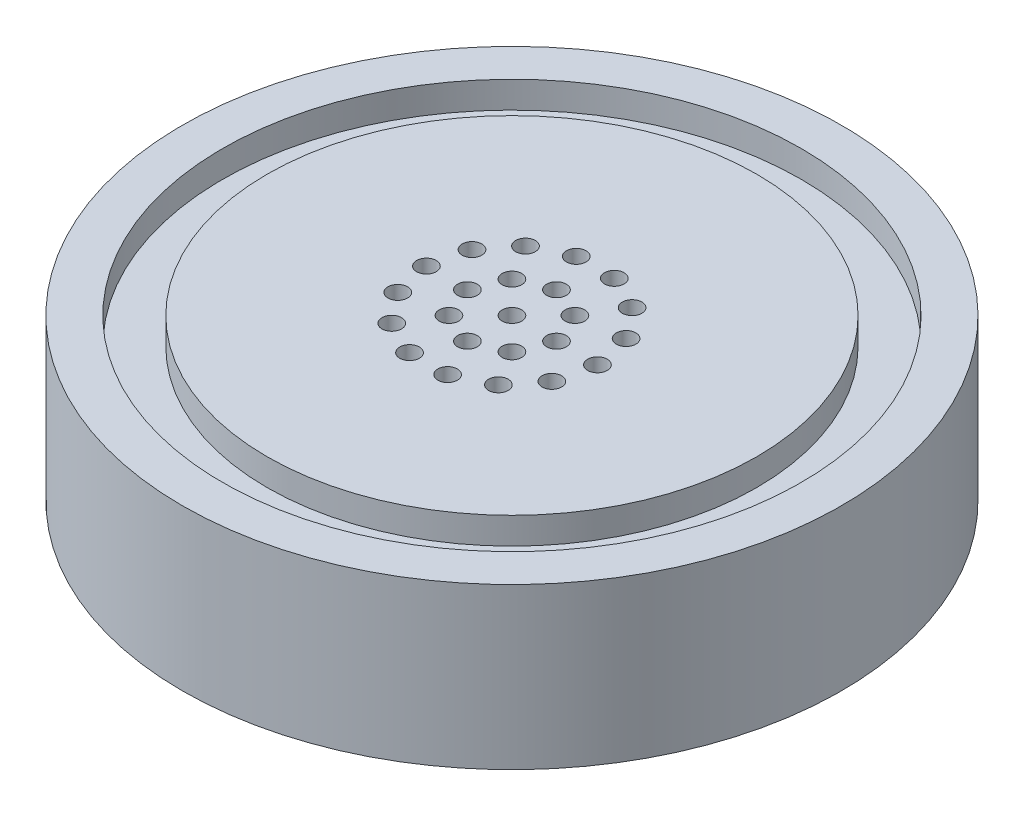
SolidWorks part; units mm, degrees
material "6061-T6 (SS)"
ref_plane "Front Plane" through (0, 0, 0) normal (0, 0, 1) x (1, 0, 0)
ref_plane "Top Plane" through (0, 0, 0) normal (0, 1, 0) x (1, 0, 0)
ref_plane "Right Plane" through (0, 0, 0) normal (1, 0, 0) x (0, 0, -1)
ref_axis "Axis1" through (0, -0.4763, 0) along (0, 1, 0)
sketch "Sketch2" plane through (0, 0, 0) normal (0, 1, 0) x (1, 0, 0)
  circle A0 centre (0, 0) radius 23.495
  dimension "D1" = 46.99
extrude "Boss-Extrude1" add sketch "Sketch2" along normal blind 11.43
hole_wizard "#54 (0.055) Diameter Hole1" positions "Sketch3" profile "Sketch4" hole size "#54" standard "ANSI Inch" end condition up to next
sketch "Sketch3" plane through (0, 11.43, 0) normal (0, 1, 0) x (1, 0, 0)
  line L0 (-6.2865, 0) -> (6.2865, 0) construction
  point P0 (-6.096, 0)
  point P12 (-3.175, 0)
  point P16 (0, 0)
  point P23 (-5.4923, 2.645)
  point P24 (-3.8008, 4.766)
  point P25 (-1.3565, 5.9432)
  point P26 (1.3565, 5.9432)
  point P27 (3.8008, 4.766)
  point P28 (5.4923, 2.645)
  point P29 (6.096, 0)
  point P30 (5.4923, -2.645)
  point P31 (3.8008, -4.766)
  point P32 (1.3565, -5.9432)
  point P33 (-1.3565, -5.9432)
  point P34 (0, 0)
  point P39 (-2.2451, 2.2451)
  point P40 (0, 3.175)
  point P41 (2.2451, 2.2451)
  point P42 (3.175, 0)
  point P43 (2.2451, -2.2451)
  point P44 (0, 0)
  point P48 (-3.8008, -4.766)
  point P49 (-5.4923, -2.645)
  point P53 (0, -3.175)
  point P54 (-2.2451, -2.2451)
  point P65 (0, 0)
  point P66 (0, 0)
  point P67 (0, 0)
  point P68 (0, 0)
  point P69 (0, 0)
  point P70 (0, 0)
  point P71 (0, 0)
  point P72 (0, 0)
  point P73 (0, 0)
  point P74 (0, 0)
  point P75 (0, 0)
  point P76 (0, 0)
  point P77 (0, 0)
  point P78 (0, 0)
  point P79 (0, 0)
  point P80 (0, 0)
  point P81 (0, 0)
  point P82 (0, 0)
  point P83 (0, 0)
  point P84 (0, 0)
  point P85 (0, 0)
  point P86 (0, 0)
  point P87 (0, 0)
  point P88 (0, 0)
  dimension "D1" = 6.096
  dimension "D2" = 3.175
  dimension "D3" = 14
  dimension "D4" = 8
sketch "Sketch4" plane through (-6.096, 11.43, 0) normal (1, 0, 0) x (0, 0, 1)
  line L0 (0, 0) -> (0, 11.43)
  line L1 (0, 11.43) -> (0.6985, 11.43)
  line L2 (0.6985, 11.43) -> (0.6985, 0)
  line L5 (0.6985, 0) -> (0, 0)
  line L11 (0, -6.35) -> (0, 107.95) construction
  dimension "Thru Hole Dia." = 1.397
  dimension "Thru Hole Depth" = 11.43
ref_plane "Plane1" through (0, 11.43, 0) normal (0, 1, 0) x (1, 0, 0)
sketch "Sketch8" plane through (0, 0, 0) normal (0, 0, 1) x (1, 0, 0)
  line L0 (27.94, 11.43) -> (-27.94, 11.43) construction
  line L1 (17.4498, 11.43) -> (20.6248, 11.43)
  line L2 (17.4498, 11.43) -> (17.4498, 9.525)
  line L3 (17.4498, 9.525) -> (20.6248, 9.525)
  line L4 (20.6248, 11.43) -> (20.6248, 9.525)
  line L6 (0, -0.4763) -> (0, 10.0012) construction
  dimension "D1" = 20.6248
  dimension "D2" = 3.175
  dimension "D3" = 1.905
revolve "Cut-Revolve1" cut sketch "Sketch8" angle 360 about axis through (0, -0.4763, 0) along (0, 1, 0)
sketch "Sketch11" plane through (0, 0, 0) normal (0, 0, 1) x (1, 0, 0)
  point P0 (-6.35, 0)
